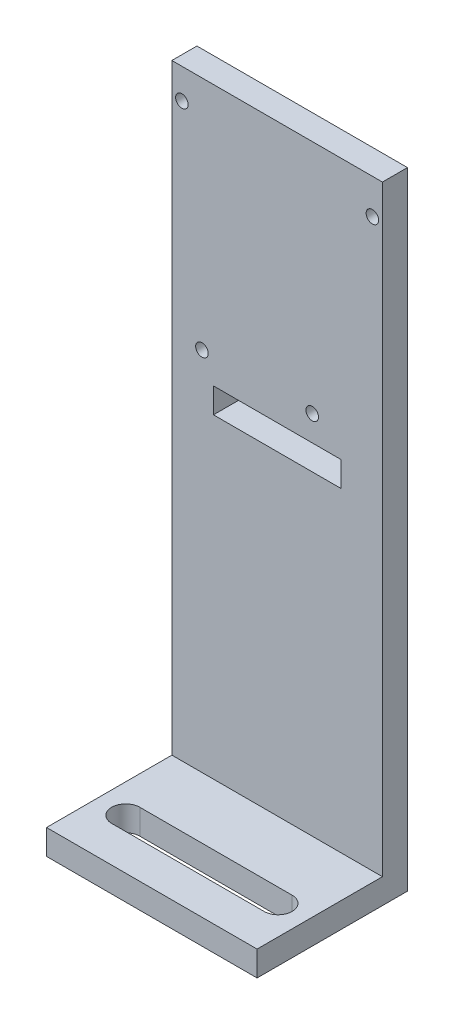
SolidWorks part; units mm, degrees
ref_plane "Front Plane" through (0, 0, 0) normal (0, 0, 1) x (1, 0, 0)
ref_plane "Top Plane" through (0, 0, 0) normal (0, 1, 0) x (1, 0, 0)
ref_plane "Right Plane" through (0, 0, 0) normal (1, 0, 0) x (0, 0, -1)
sketch "Sketch1" plane through (0, 0, 0) normal (0, 0, 1) x (1, 0, 0)
  line L0 (-43.7614, 78.5105) -> (9.5786, 78.5105) construction
  line L1 (-43.7614, 129.3105) -> (9.5786, 129.3105)
  line L2 (-43.7614, 129.3105) -> (-43.7614, -29.4395)
  line L3 (-43.7614, -29.4395) -> (9.5786, -29.4395)
  line L4 (9.5786, 129.3105) -> (9.5786, -29.4395)
  line L5 (-43.7614, 69.6205) -> (9.5786, 69.6205) construction
  line L6 (-43.7614, 121.6905) -> (9.5786, 121.6905) construction
  line L7 (-43.7614, 120.4205) -> (9.5786, 120.4205) construction
  circle A0 centre (-36.1414, 69.6205) radius 1.5875
  circle A1 centre (-8.2014, 69.6205) radius 1.5875
  circle A2 centre (-41.2214, 121.6905) radius 1.5875
  circle A4 centre (7.0386, 120.4205) radius 1.5875
  dimension "D5" = 3.175
  dimension "D7" = 3.175
  dimension "D8" = 27.94
  dimension "D10" = 3.175
  dimension "D11" = 1.27
  dimension "D13" = 3.175
  dimension "D1" = 158.75
  dimension "D2" = 53.34
  dimension "D3" = 107.95
  dimension "D4" = 8.89
  dimension "D6" = 7.62
  dimension "D9" = 52.07
  dimension "D12" = 2.54
  dimension "D14" = 48.26
extrude "Boss-Extrude1" add sketch "Sketch1" along normal blind 6.35
sketch "Sketch2" plane through (0, 0, 6.35) normal (0, 0, 1) x (1, 0, 0)
  line L0 (-43.7614, 78.5105) -> (9.5786, 78.5105) construction
  line L1 (-43.7614, 129.3105) -> (-43.7614, -29.4395) construction
  line L2 (9.5786, -29.4395) -> (9.5786, 129.3105) construction
  line L3 (-43.7614, -29.4395) -> (9.5786, -29.4395) construction
  line L5 (-33.2204, 63.1891) -> (-0.9624, 63.1891)
  line L6 (-33.2204, 63.1891) -> (-33.2204, 56.8391)
  line L7 (-33.2204, 56.8391) -> (-0.9624, 56.8391)
  line L8 (-0.9624, 63.1891) -> (-0.9624, 56.8391)
  circle A0 centre (-17.0914, 78.5105) radius 12.573 construction
  point P14 (-17.0914, 56.8391)
  dimension "D2" = 25.146
  dimension "D1" = 107.95
  dimension "D3" = 32.258
  dimension "D4" = 6.35
  dimension "D5" = 26.67
extrude "Boss-Extrude2" [suppressed] add sketch "Sketch2" along normal blind 31.75
sketch "Sketch3" [suppressed] plane through (0, 63.1891, 0) normal (0, 1, 0) x (1, 0, 0)
  line L0 (-1.2164, -38.1) -> (-1.2164, -6.35) construction
  line L1 (-32.9664, -38.1) -> (-1.2164, -38.1)
  line L2 (-32.9664, -38.1) -> (-32.9664, -31.75)
  line L3 (-32.9664, -31.75) -> (-1.2164, -31.75)
  line L4 (-1.2164, -38.1) -> (-1.2164, -31.75)
  dimension "D1" = 6.35
extrude "Boss-Extrude3" [suppressed] add sketch "Sketch3" along normal blind 12.7
sketch "Sketch4" [suppressed] plane through (0, 0, 38.1) normal (0, 0, 1) x (1, 0, 0)
  line L0 (-43.7614, 78.5105) -> (9.5786, 78.5105) construction
  line L1 (-43.7614, 129.3105) -> (-43.7614, -29.4395) construction
  line L2 (9.5786, -29.4395) -> (9.5786, 129.3105) construction
  line L3 (-43.7614, -29.4395) -> (9.5786, -29.4395) construction
  circle A0 centre (-17.0914, 78.5105) radius 12.573
  dimension "D2" = 25.146
  dimension "D1" = 107.95
extrude "Cut-Extrude1" [suppressed] cut sketch "Sketch4" against normal up to next
sketch "Sketch5" [suppressed] plane through (0, 63.1891, 0) normal (0, 1, 0) x (1, 0, 0)
  line L0 (-1.2164, -38.1) -> (-1.2164, -31.75) construction
  line L1 (-32.9664, -31.75) -> (-1.2164, -31.75)
  line L2 (-32.9664, -31.75) -> (-32.9664, -34.4212)
  line L3 (-32.9664, -34.4212) -> (-1.2164, -34.4212)
  line L4 (-1.2164, -31.75) -> (-1.2164, -34.4212)
  line L5 (-32.9664, -31.75) -> (-32.9664, -38.1) construction
  line L6 (-1.2164, -38.1) -> (-32.9664, -38.1)
  line L7 (-1.2164, -38.1) -> (-1.2164, -35.6712)
  line L8 (-1.2164, -35.6712) -> (-32.9664, -35.6712)
  line L9 (-32.9664, -38.1) -> (-32.9664, -35.6712)
  dimension "D1" = 1.25
  dimension "D2" = 2.6712
extrude "Boss-Extrude4" [suppressed] add sketch "Sketch5" along normal blind 6.35
fillet "Fillet1" [suppressed] radius 5.08
extrude "Cut-Extrude2" cut sketch "Sketch2<3>" against normal through all
sketch "Sketch2<3>" plane through (0, 0, 6.35) normal (0, 0, 1) x (1, 0, 0) same geometry as "Sketch2"
sketch "Sketch6" plane through (0, 0, 6.35) normal (0, 0, 1) x (1, 0, 0)
  line L0 (9.5786, -29.4395) -> (9.5786, 129.3105) construction
  line L1 (-43.7614, -29.4395) -> (9.5786, -29.4395)
  line L2 (-43.7614, -29.4395) -> (-43.7614, -23.0895)
  line L3 (-43.7614, -23.0895) -> (9.5786, -23.0895)
  line L4 (9.5786, -29.4395) -> (9.5786, -23.0895)
  dimension "D1" = 6.35
extrude "Boss-Extrude5" add sketch "Sketch6" along normal blind 31.75
sketch "Sketch7" plane through (0, -23.0895, 0) normal (0, 1, 0) x (1, 0, 0)
  line L0 (-36.3954, -25.4) -> (2.2126, -25.4) construction
  line L1 (9.5786, -38.1) -> (-43.7614, -38.1) construction
  line L2 (-43.7614, -38.1) -> (-43.7614, -6.35) construction
  line L3 (9.5786, -38.1) -> (9.5786, -6.35) construction
  line L4 (-36.3954, -21.844) -> (2.2126, -21.844)
  line L5 (-36.3954, -28.956) -> (2.2126, -28.956)
  arc A0 (-36.3954, -21.844) -> (-36.3954, -28.956) centre (-36.3954, -25.4) ccw
  arc A1 (2.2126, -28.956) -> (2.2126, -21.844) centre (2.2126, -25.4) ccw
  dimension "D4" = 7.112
  dimension "D5" = 7.112
  dimension "D1" = 12.7
  dimension "D2" = 7.366
  dimension "D3" = 7.366
extrude "Cut-Extrude3" cut sketch "Sketch7" against normal up to next
